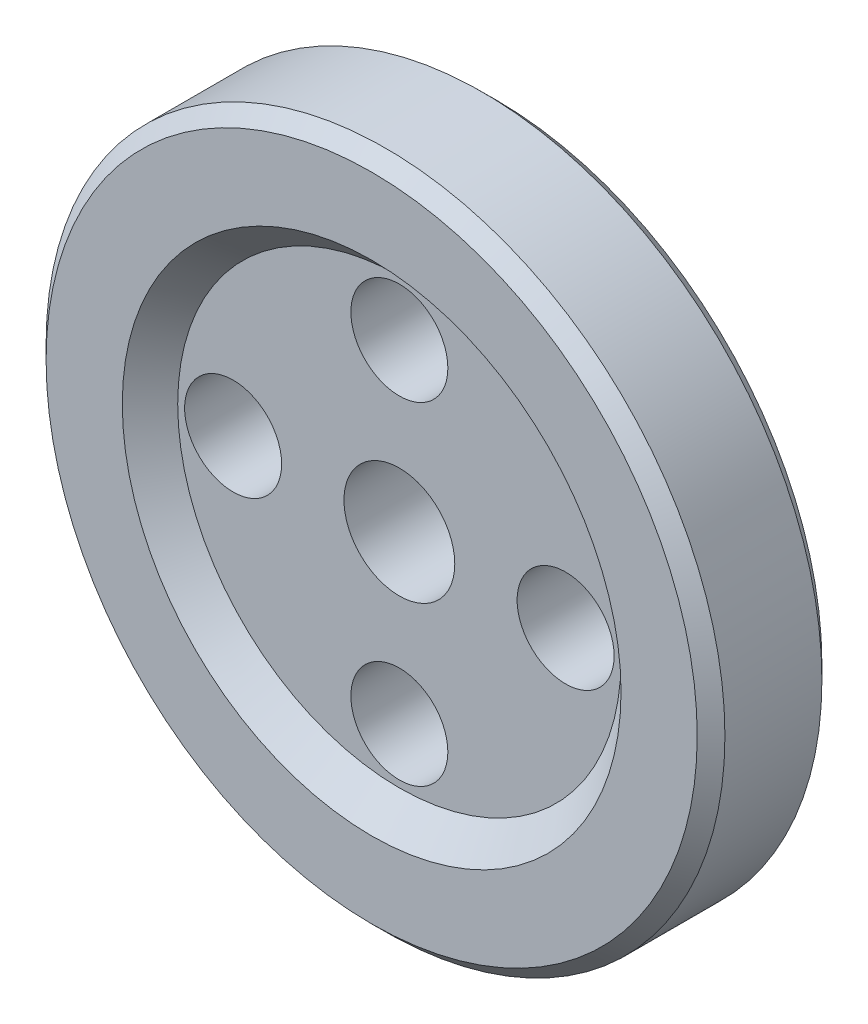
SolidWorks part; units mm, degrees
ref_plane "Front Plane" through (0, 0, 0) normal (0, 0, 1) x (1, 0, 0)
ref_plane "Top Plane" through (0, 0, 0) normal (0, 1, 0) x (1, 0, 0)
ref_plane "Right Plane" through (0, 0, 0) normal (1, 0, 0) x (0, 0, -1)
sketch "Sketch1" plane through (0, 0, 0) normal (0, 0, 1) x (1, 0, 0)
  line L0 (0, 54.0321) -> (0, -56.8947) construction
  line L1 (-62.164, 0) -> (60.6979, 0) construction
  circle A0 centre (0, 0) radius 16
  circle A1 centre (0, 0) radius 18
  circle A2 centre (0, 0) radius 24.5
  circle A4 centre (0, 12) radius 3.5
  circle A5 centre (12, 0) radius 3.5
  circle A6 centre (0, -12) radius 3.5
  circle A7 centre (-12, 0) radius 3.5
  circle A8 centre (0, 0) radius 4
  point P21 (0, 0)
  dimension "D1" = 32
  dimension "D2" = 36
  dimension "D3" = 49
  dimension "D5" = 7
  dimension "D7" = 8
  dimension "D6" = 4
extrude "Boss-Extrude1" add sketch "Sketch1" along normal blind 9 contours A2 A1 region at (-23.807, 0, 0)
extrude "Boss-Extrude2" add sketch "Sketch1<3>" along normal blind 7 contours A0 A8 A7 A6 A5 A4 | A1 A0 region at (-15.5475, 0, 0) region at (-17.4909, 0, 0)
sketch "Sketch1<3>" plane through (0, 0, 0) normal (0, 0, 1) x (1, 0, 0) same geometry as "Sketch1"
sketch "Sketch3" plane through (0, 0, 0) normal (0, 1, 0) x (1, 0, 0)
  line L0 (-18, -9) -> (-16, -7)
  line L1 (-18, -7) -> (18, -7) construction
  line L2 (0, 3.7718) -> (0, -12.284) construction
  line L3 (-18, -9) -> (-18, -7)
  line L4 (-18, -7) -> (-16, -7)
revolve "Revolve2" add sketch "Sketch3" angle 360 about L2
sketch "Sketch4" plane through (0, 0, 0) normal (0, 1, 0) x (1, 0, 0)
  line L0 (-24.5, -8) -> (-23.5, -9)
  line L1 (-24.5, 0) -> (-24.5, -9) construction
  line L2 (-24.5, -9) -> (24.5, -9) construction
  line L3 (-24.5, -1) -> (-23.5, 0)
  line L4 (24.5, 0) -> (-24.5, 0) construction
  line L5 (-24.5, -8) -> (-24.5, -9)
  line L6 (-24.5, -9) -> (-23.5, -9)
  line L7 (-24.5, -1) -> (-24.5, 0)
  line L8 (-24.5, 0) -> (-23.5, 0)
  line L9 (0, 7.5512) -> (0, -12.7557) construction
  dimension "D1" = 1
  dimension "D2" = 45
  dimension "D3" = 1
  dimension "D4" = 45
revolve "Cut-Revolve1" cut sketch "Sketch4" angle 360 about L9
